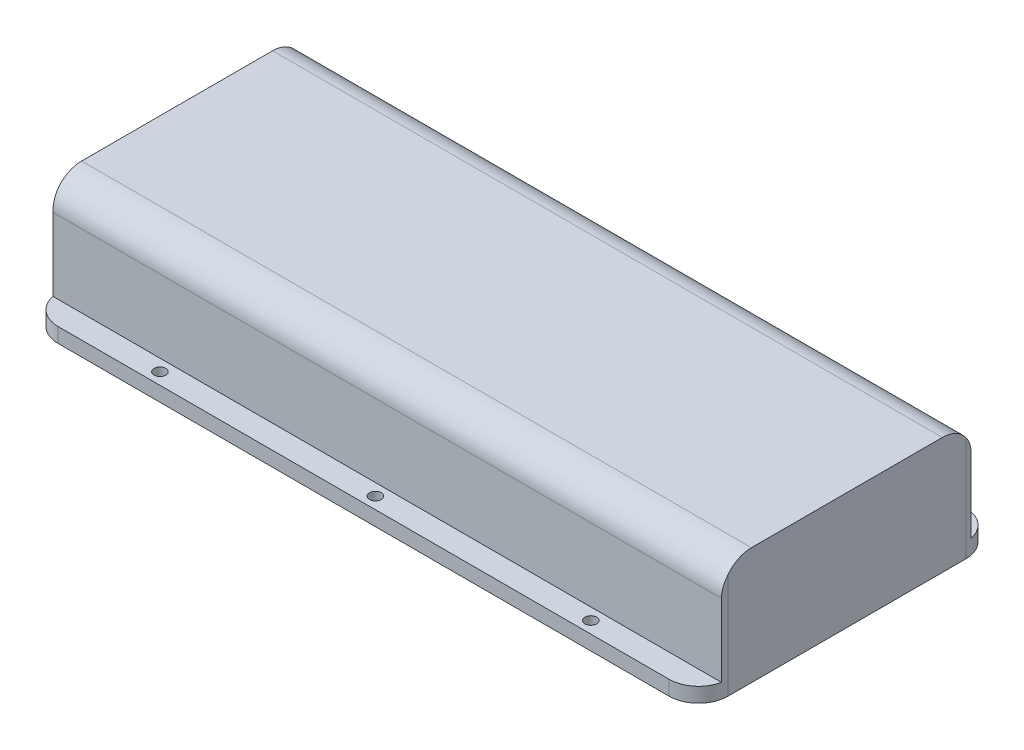
SolidWorks part; units mm, degrees
ref_plane "Front Plane" through (0, 0, 0) normal (0, 0, 1) x (1, 0, 0)
ref_plane "Top Plane" through (0, 0, 0) normal (0, 1, 0) x (1, 0, 0)
ref_plane "Right Plane" through (0, 0, 0) normal (1, 0, 0) x (0, 0, -1)
sketch "Sketch1" plane through (0, 0, 0) normal (0, 1, 0) x (1, 0, 0)
  line L1 (0, 0) -> (228, 0)
  line L2 (0, 0) -> (0, 101)
  line L3 (0, 101) -> (228, 101)
  line L4 (228, 0) -> (228, 101)
  dimension "D1" = 228
  dimension "D2" = 101
extrude "Boss-Extrude1" add sketch "Sketch1" along normal blind 5
sketch "Sketch2" plane through (0, 5, 0) normal (0, 1, 0) x (1, 0, 0)
  line L0 (0, 50.5) -> (228, 50.5) construction
  line L1 (0, 101) -> (0, 0) construction
  line L2 (228, 0) -> (228, 101) construction
  line L3 (187.34, 97) -> (40.66, 97) construction
  line L4 (187.34, 4) -> (40.66, 4) construction
  circle A0 centre (187.34, 97) radius 2
  circle A1 centre (187.34, 4) radius 2
  circle A2 centre (114, 97) radius 2
  circle A3 centre (40.66, 97) radius 2
  circle A4 centre (114, 4) radius 2
  circle A5 centre (40.66, 4) radius 2
  dimension "D1" = 4
  dimension "D2" = 93
  dimension "D3" = 40.66
  dimension "D4" = 73.34
  dimension "D5" = 73.34
extrude "Cut-Extrude1" cut sketch "Sketch2" against normal through all
sketch "Sketch3" plane through (0, 5, 0) normal (0, 1, 0) x (1, 0, 0)
  line L0 (228, 0) -> (228, 101) construction
  line L1 (0, 93) -> (228, 93)
  line L2 (0, 93) -> (0, 8)
  line L3 (0, 8) -> (228, 8)
  line L4 (228, 93) -> (228, 8)
  line L5 (0, 101) -> (0, 0) construction
  line L6 (0, 50.5) -> (228, 50.5) construction
  line L7 (0, 50.5) -> (228, 50.5) construction
  dimension "D1" = 85
extrude "Boss-Extrude2" add sketch "Sketch3" along normal blind 34.8
sketch "Sketch4" plane through (0, 0, 0) normal (-1, 0, 0) x (0, 0, 1)
  line L1 (-50.3378, 25.4675) -> (-31.311, 25.4675)
  line L2 (-50.3378, 25.4675) -> (-50.3378, 17.9)
  line L3 (-50.3378, 17.9) -> (-31.311, 17.9)
  line L4 (-31.311, 25.4675) -> (-31.311, 17.9)
extrude "Boss-Extrude3" add sketch "Sketch4" along normal blind 2.2
fillet "Fillet1" radius 10 6 edges at (0, 2.5, -101) (228, 2.5, -101) (228, 2.5, 0) (0, 2.5, 0) (114, 39.8, -93) (114, 39.8, -8)
